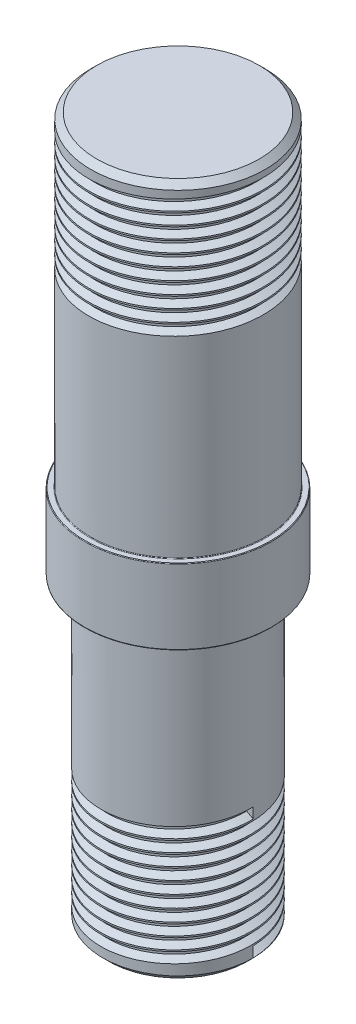
SolidWorks part; units mm, degrees
ref_plane "Płaszczyzna przednia" through (0, 0, 0) normal (0, 0, 1) x (1, 0, 0)
ref_plane "Płaszczyzna górna" through (0, 0, 0) normal (0, 1, 0) x (1, 0, 0)
ref_plane "Płaszczyzna prawa" through (0, 0, 0) normal (1, 0, 0) x (0, 0, -1)
sketch "Szkic1" plane through (0, 0, 0) normal (0, 0, 1) x (1, 0, 0)
  line L0 (0, 0) -> (0, 116.5) construction
  line L1 (0, 0) -> (11.5, 0)
  line L2 (12.5, 1) -> (12.5, 49.9)
  line L3 (12.6, 50) -> (15.4, 50)
  line L4 (15.5, 50.1) -> (15.5, 62.4)
  line L5 (15.4, 62.5) -> (14.6, 62.5)
  line L6 (14.5, 62.6) -> (14.5, 115.5)
  line L7 (13.5, 116.5) -> (0, 116.5)
  line L8 (14.5, 115.5) -> (13.5, 116.5)
  line L9 (11.5, 0) -> (12.5, 1)
  line L10 (0, 0) -> (0, 116.5)
  arc A0 (15.4, 50) -> (15.5, 50.1) centre (15.4, 50.1) ccw
  arc A1 (15.5, 62.4) -> (15.4, 62.5) centre (15.4, 62.4) ccw
  arc A2 (14.5, 62.6) -> (14.6, 62.5) centre (14.6, 62.6) ccw
  arc A3 (12.5, 49.9) -> (12.6, 50) centre (12.6, 49.9) cw
  point P5 (12.5, 0)
  point P10 (14.5, 116.5)
  point P16 (15.5, 50)
  point P19 (15.5, 62.5)
  point P22 (14.5, 62.5)
  point P25 (12.5, 50)
  dimension "D8" = 0.1
  dimension "D1" = 12.5
  dimension "D2" = 50
  dimension "D3" = 3
  dimension "D4" = 12.5
  dimension "D5" = 1
  dimension "D6" = 54
  dimension "D7" = 14.5
revolve "Obrót1" add sketch "Szkic1" angle 360 about L0
thread "Gwint1" pitch 2 method cut profile "Profil gwintu1" start angle 0, offset 0, length 20, pitch 2, diameter 29
ref_plane "Płaszczyzna4" through (-14.5, 115.5, 0) normal (0, 0, 1) x (-1, 0, 0)
sketch "Profil gwintu1" plane through (-14.5, 115.5, 0) normal (0, 0, 1) x (-1, 0, 0)
  line L0 (0, 0) -> (0, 2) construction
  line L11 (0, 0) -> (0, 1.75)
  line L12 (0, 1.75) -> (-1.0825, 1.125)
  line L13 (-1.0825, 1.125) -> (-1.0825, 0.625)
  line L15 (-1.0825, 0.625) -> (0, 0)
  line L17 (-1.0825, 0.875) -> (0, 0.875) construction
  point P2 (0, 0)
  dimension "Pitch" = 2
  dimension "Profile_Angle" = 60
  dimension "Profile_Land" = 0.5
  dimension "Profile_Height" = 1.0825
thread "Gwint2" pitch 2 method cut profile "Profil gwintu2" start angle 0, offset 0, length 20, pitch 2, diameter 25
ref_plane "Płaszczyzna5" through (12.5, 1, 0) normal (0, 0, 1) x (1, 0, 0)
sketch "Profil gwintu2" plane through (12.5, 1, 0) normal (0, 0, 1) x (1, 0, 0)
  line L0 (0, 0) -> (0, 2) construction
  line L11 (0, 0) -> (0, 1.75)
  line L12 (0, 1.75) -> (-1.0825, 1.125)
  line L13 (-1.0825, 1.125) -> (-1.0825, 0.625)
  line L15 (-1.0825, 0.625) -> (0, 0)
  line L17 (-1.0825, 0.875) -> (0, 0.875) construction
  point P2 (0, 0)
  dimension "Pitch" = 2
  dimension "Profile_Angle" = 60
  dimension "Profile_Land" = 0.5
  dimension "Profile_Height" = 1.0825
